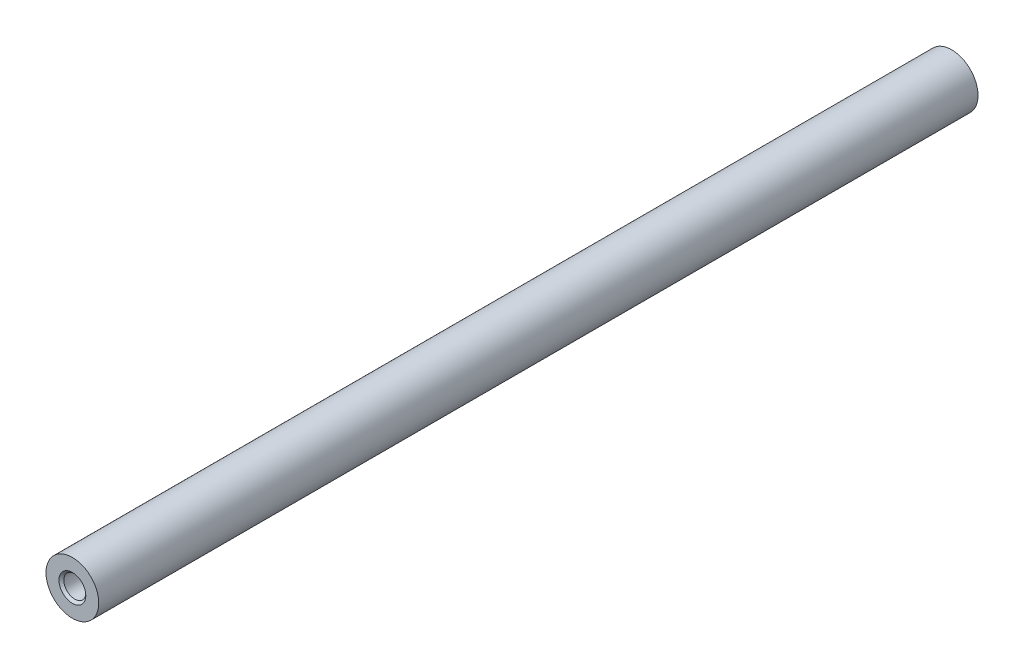
SolidWorks part; units mm, degrees
material "6061 合金"
ref_plane "前视基准面" through (0, 0, 0) normal (0, 0, 1) x (1, 0, 0)
ref_plane "上视基准面" through (0, 0, 0) normal (0, 1, 0) x (1, 0, 0)
ref_plane "右视基准面" through (0, 0, 0) normal (1, 0, 0) x (0, 0, -1)
sketch "草图1" plane through (0, 0, 0) normal (0, 0, 1) x (1, 0, 0)
  circle A0 centre (0, 0) radius 3
  dimension "D1" = 6
extrude "凸台-拉伸1" add sketch "草图1" along normal blind 100
hole_wizard "M3 螺纹孔1" positions "草图4" profile "草图3" tap size "M3" standard "GB" end condition through all
sketch "草图4" plane through (0, 0, 100) normal (0, 0, 1) x (1, 0, 0)
  point P0 (0, 0)
sketch "草图3" plane through (0, 0, 100) normal (1, 0, 0) x (0, -1, 0)
  line L0 (0, 0) -> (0, 100)
  line L1 (0, 100) -> (1.25, 100)
  line L2 (1.25, 100) -> (1.25, 0.275)
  line L3 (1.25, 0.275) -> (1.525, 0)
  line L5 (1.525, 0) -> (0, 0)
  line L6 (-1.25, 0.275) -> (-1.525, 0) construction
  line L11 (0, -6.35) -> (0, 107.95) construction
  dimension "通孔螺纹孔钻头直径" = 2.5
  dimension "通孔螺纹孔钻头深度" = 100
  dimension "近端锥形沉头孔直径" = 3.05
  dimension "近端锥形沉头孔角度" = 90
cosmetic thread "孔螺蚊线1" parameters "D2"=3
